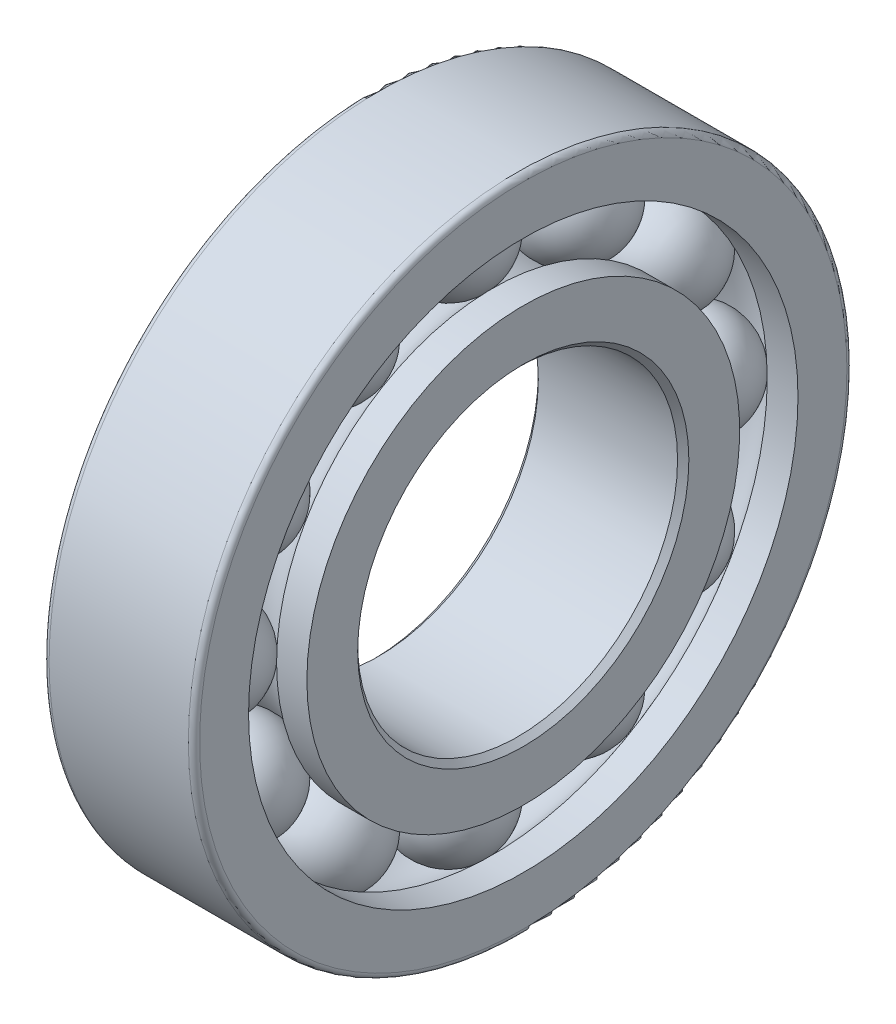
SolidWorks part; units mm, degrees
ref_plane "Front Plane" through (0, 0, 0) normal (0, 0, 1) x (1, 0, 0)
ref_plane "Top Plane" through (0, 0, 0) normal (0, 1, 0) x (1, 0, 0)
ref_plane "Right Plane" through (0, 0, 0) normal (1, 0, 0) x (0, 0, -1)
sketch "Sketch1" plane through (0, 0, 0) normal (0, 1, 0) x (1, 0, 0)
  line L0 (-25.3067, 0) -> (0, 0) construction
  line L1 (0, 0) -> (0, 16.05) construction
  line L3 (4, 17.5) -> (-4, 17.5)
  line L4 (4, 17.5) -> (4, 14.6)
  line L5 (4, 14.6) -> (-4, 14.6)
  line L6 (-4, 17.5) -> (-4, 14.6)
  line L7 (4, 17.5) -> (-4, 14.6) construction
  line L8 (4, 14.6) -> (-4, 17.5) construction
  line L9 (4, 11.5) -> (-4, 11.5)
  line L10 (4, 11.5) -> (4, 8.5)
  line L11 (4, 8.5) -> (-4, 8.5)
  line L12 (-4, 11.5) -> (-4, 8.5)
  line L13 (4, 11.5) -> (-4, 8.5) construction
  line L14 (4, 8.5) -> (-4, 11.5) construction
  circle A0 centre (0, 13.0311) radius 2.8381
  point P8 (0, 10)
  dimension "D1" = 8.5
  dimension "D2" = 11.5
  dimension "D3" = 14.6
  dimension "D4" = 17.5
  dimension "D5" = 8
revolve "Revolve1" add sketch "Sketch1" angle 360 about L0 region at (0, 0, -16.2573) region at (0, 0, -9.7831)
ref_axis "Axis1" through (4, 0, 0) along (-1, 0, 0)
sketch "Sketch2" plane through (0, 0, 0) normal (0, 0, 1) x (1, 0, 0)
  line L0 (2.8, 13.03) -> (-2.8, 13.03)
  circle A0 centre (0, 13.03) radius 2.8
  point P5 (0, 0)
  dimension "D1" = 5.6
  dimension "D2" = 13.03
revolve "Revolve2" add sketch "Sketch2" angle 360 about L0 region at (0, 14.2184, 0)
pattern_circular "CirPattern3" count 12 over 360 about axis through (4, 0, 0) along (-1, 0, 0) of bodies 103
fillet "Fillet1" radius 0.3 2 edges at (4, 0, 17.5) (-4, 0, 17.5)
chamfer "Chamfer1" distance 0.3 angle 45 2 edges at (4, 0, 8.5) (-4, 0, 8.5)
